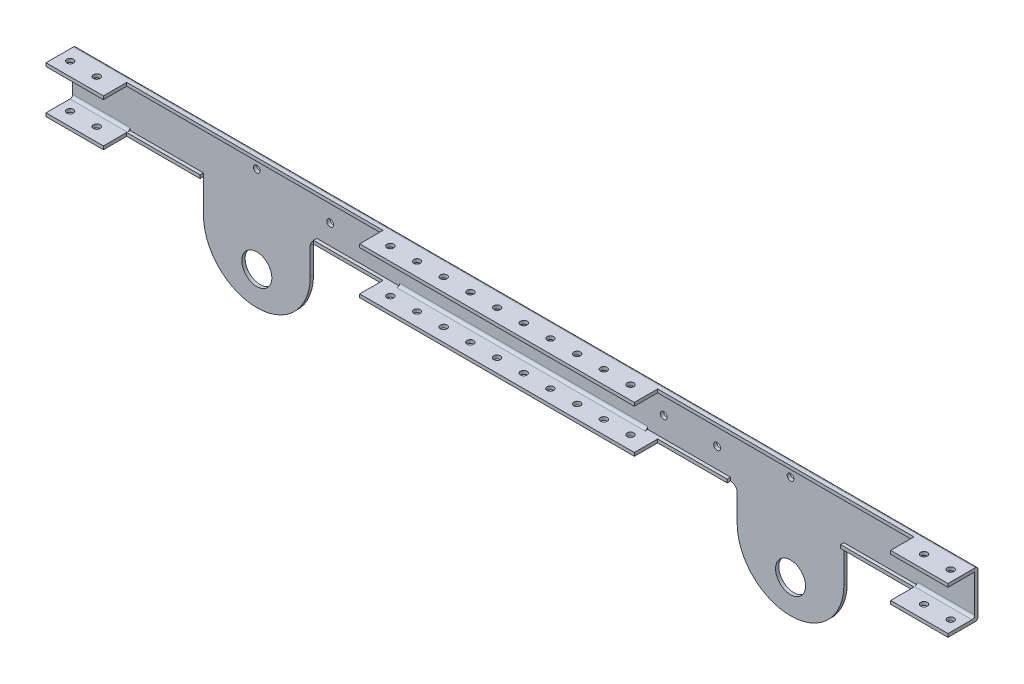
SolidWorks part; units mm, degrees
ref_plane "Front Plane" through (0, 0, 0) normal (0, 0, 1) x (1, 0, 0)
ref_plane "Top Plane" through (0, 0, 0) normal (0, 1, 0) x (1, 0, 0)
ref_plane "Right Plane" through (0, 0, 0) normal (1, 0, 0) x (0, 0, -1)
sketch "Sketch1" plane through (0, 0, 0) normal (0, 0, 1) x (1, 0, 0)
  line L0 (50.8, 0) -> (50.8, 25.4)
  line L1 (-50.8, 0) -> (-50.8, 76.2)
  line L2 (57.15, 31.75) -> (438.15, 31.75)
  line L3 (444.5, 25.4) -> (444.5, 0)
  line L4 (546.1, 0) -> (546.1, 76.2)
  line L5 (-50.8, 76.2) -> (546.1, 76.2)
  arc A0 (-50.8, 0) -> (50.8, 0) centre (0, 0) ccw
  arc A1 (50.8, 25.4) -> (57.15, 31.75) centre (57.15, 25.4) cw
  arc A2 (438.15, 31.75) -> (444.5, 25.4) centre (438.15, 25.4) cw
  arc A3 (444.5, 0) -> (546.1, 0) centre (495.3, 0) ccw
  circle A4 centre (0, 0) radius 6.35
  circle A5 centre (495.3, 0) radius 6.35
  dimension "D1" = 101.6
  dimension "D2" = 6.35
  dimension "D4" = 6.35
  dimension "D6" = 76.2
  dimension "D3" = 381
  dimension "D5" = 25.4
  dimension "D7" = 76.2
extrude "Boss-Extrude1" add sketch "Sketch1" along normal blind 3.175
sketch "Sketch2" plane through (0, 0, 3.175) normal (0, 0, 1) x (1, 0, 0)
  line L0 (-50.8, 76.2) -> (-50.8, 73.025)
  line L1 (-50.8, 76.2) -> (-50.8, 0) construction
  line L2 (546.1, 76.2) -> (-50.8, 76.2)
  line L3 (-50.8, 73.025) -> (546.1, 73.025)
  line L4 (546.1, 0) -> (546.1, 76.2) construction
  line L5 (546.1, 73.025) -> (546.1, 76.2)
  dimension "D1" = 3.175
extrude "Boss-Extrude2" add sketch "Sketch2" along normal blind 25.4
fillet "Fillet1" radius 2.54 2 edges at (247.65, 76.2, 0)
sketch "Sketch3" plane through (0, 76.2, 0) normal (0, 1, 0) x (1, 0, 0)
  line L0 (546.1, -28.575) -> (546.1, -2.54)
  circle A0 centre (527.05, -15.5575) radius 3.2639
  circle A1 centre (501.65, -15.5575) radius 3.2639
  circle A2 centre (476.25, -15.5575) radius 3.2639
  circle A3 centre (450.85, -15.5575) radius 3.2639
  circle A4 centre (425.45, -15.5575) radius 3.2639
  circle A5 centre (400.05, -15.5575) radius 3.2639
  circle A6 centre (374.65, -15.5575) radius 3.2639
  circle A7 centre (349.25, -15.5575) radius 3.2639
  circle A8 centre (323.85, -15.5575) radius 3.2639
  circle A9 centre (298.45, -15.5575) radius 3.2639
  circle A10 centre (273.05, -15.5575) radius 3.2639
  circle A11 centre (247.65, -15.5575) radius 3.2639
  circle A12 centre (222.25, -15.5575) radius 3.2639
  circle A13 centre (196.85, -15.5575) radius 3.2639
  circle A14 centre (171.45, -15.5575) radius 3.2639
  circle A15 centre (146.05, -15.5575) radius 3.2639
  circle A16 centre (120.65, -15.5575) radius 3.2639
  circle A17 centre (95.25, -15.5575) radius 3.2639
  circle A18 centre (69.85, -15.5575) radius 3.2639
  circle A19 centre (44.45, -15.5575) radius 3.2639
  circle A20 centre (19.05, -15.5575) radius 3.2639
  circle A21 centre (-6.35, -15.5575) radius 3.2639
  circle A22 centre (-31.75, -15.5575) radius 3.2639
  dimension "D1" = 19.05
  dimension "D2" = 23
extrude "Cut-Extrude1" cut sketch "Sketch3" against normal blind 25.4 contours A0 | A1 | A2 | A3 | A22 | A21 | A20 | A19 | A18 | A17 | A16 | A15 | A14 | A13 | A12 | A11 | A10 | A9 | A8 | A7 | A6 | A5 | A4 region at (527.05, 76.2, 15.5575) region at (501.65, 76.2, 15.5575) region at (476.25, 76.2, 15.5575) region at (450.85, 76.2, 15.5575) region at (425.45, 76.2, 15.5575) region at (400.05, 76.2, 15.5575) region at (374.65, 76.2, 15.5575) region at (349.25, 76.2, 15.5575) region at (323.85, 76.2, 15.5575) region at (298.45, 76.2, 15.5575) region at (273.05, 76.2, 15.5575) region at (247.65, 76.2, 15.5575) region at (222.25, 76.2, 15.5575) region at (196.85, 76.2, 15.5575) region at (171.45, 76.2, 15.5575) region at (146.05, 76.2, 15.5575) region at (120.65, 76.2, 15.5575) region at (95.25, 76.2, 15.5575) region at (69.85, 76.2, 15.5575) region at (44.45, 76.2, 15.5575) region at (19.05, 76.2, 15.5575) region at (-6.35, 76.2, 15.5575) region at (-31.75, 76.2, 15.5575)
sketch "Sketch5" plane through (0, 0, 0) normal (0, 0, -1) x (-1, 0, 0)
  line L0 (-444.5, 25.4) -> (-444.5, 0) construction
  circle A0 centre (-425.45, 53.975) radius 3.2639
  circle A1 centre (-374.65, 53.975) radius 3.2639
  circle A2 centre (-323.85, 53.975) radius 3.2639
  circle A3 centre (-273.05, 53.975) radius 3.2639
  circle A4 centre (-222.25, 53.975) radius 3.2639
  circle A5 centre (-171.45, 53.975) radius 3.2639
  circle A6 centre (-120.65, 53.975) radius 3.2639
  circle A7 centre (-69.85, 53.975) radius 3.2639
  dimension "D1" = 6.5278
  dimension "D2" = 19.05
  dimension "D3" = 8
extrude "Cut-Extrude2" cut sketch "Sketch5" against normal blind 25.4
sketch "Sketch6" plane through (0, 0, 3.175) normal (0, 0, 1) x (1, 0, 0)
  line L1 (-50.8, 76.2) -> (-82.55, 76.2)
  line L2 (-50.8, 76.2) -> (-50.8, 31.75)
  line L3 (-50.8, 31.75) -> (-82.55, 31.75)
  line L4 (-82.55, 76.2) -> (-82.55, 31.75)
  line L5 (546.1, 76.2) -> (577.85, 76.2)
  line L6 (546.1, 76.2) -> (546.1, 31.75)
  line L7 (546.1, 31.75) -> (577.85, 31.75)
  line L8 (577.85, 76.2) -> (577.85, 31.75)
  dimension "D1" = 31.75
  dimension "D2" = 31.75
extrude "Boss-Extrude3" add sketch "Sketch6" against normal blind 3.175
sketch "Sketch7" plane through (0, 0, 3.175) normal (0, 0, 1) x (1, 0, 0)
  line L1 (57.15, 31.75) -> (438.15, 31.75) construction
  line L2 (-50.8, 73.025) -> (-82.55, 73.025)
  line L3 (-50.8, 73.025) -> (-50.8, 76.2)
  line L4 (-50.8, 76.2) -> (-82.55, 76.2)
  line L5 (-82.55, 31.75) -> (-50.8, 31.75)
  line L6 (-82.55, 31.75) -> (-82.55, 34.925)
  line L7 (-82.55, 34.925) -> (-50.8, 34.925)
  line L8 (-50.8, 31.75) -> (-50.8, 34.925)
  line L9 (577.85, 31.75) -> (577.85, 76.2) construction
  line L10 (546.1, 76.2) -> (577.85, 76.2)
  line L11 (546.1, 76.2) -> (546.1, 73.025)
  line L12 (546.1, 73.025) -> (577.85, 73.025)
  line L13 (577.85, 76.2) -> (577.85, 73.025)
  line L14 (-82.55, 73.025) -> (-82.55, 76.2)
  line L15 (577.85, 31.75) -> (546.1, 31.75)
  line L16 (577.85, 31.75) -> (577.85, 34.925)
  line L17 (577.85, 34.925) -> (546.1, 34.925)
  line L18 (546.1, 31.75) -> (546.1, 34.925)
  line L19 (57.15, 31.75) -> (438.15, 31.75)
  line L20 (57.15, 31.75) -> (57.15, 34.925)
  line L21 (57.15, 34.925) -> (438.15, 34.925)
  line L22 (438.15, 31.75) -> (438.15, 34.925)
  arc A0 (57.15, 31.75) -> (50.8, 25.4) centre (57.15, 25.4) ccw construction
  dimension "D1" = 3.175
  dimension "D2" = 3.175
  dimension "D3" = 3.175
extrude "Boss-Extrude4" add sketch "Sketch7" along normal blind 25.4
fillet "Fillet2" radius 2.54 16 edges at (-50.8, 15.875, 0) (0, -50.8, 0) (50.8, 12.7, 0) (52.6599, 29.8901, 0) (546.1, 15.875, 0) (495.3, -50.8, 0) (444.5, 12.7, 0) (442.6401, 29.8901, 0) (-66.675, 34.925, 3.175) (-66.675, 31.75, 0) (247.65, 31.75, 0) (247.65, 34.925, 3.175) (561.975, 34.925, 3.175) (561.975, 31.75, 0) (561.975, 76.2, 0) (-66.675, 76.2, 0)
sketch "Sketch8" plane through (0, 76.2, 0) normal (0, 1, 0) x (1, 0, 0)
  circle A0 centre (-31.75, -15.5575) radius 3.2639 construction
  circle A1 centre (-31.75, -15.5575) radius 3.2639
  circle A2 centre (-57.15, -15.5575) radius 3.2639
  circle A3 centre (-31.75, -15.5575) radius 3.2639
  circle A4 centre (-6.35, -15.5575) radius 3.2639
  circle A5 centre (19.05, -15.5575) radius 3.2639
  circle A6 centre (44.45, -15.5575) radius 3.2639
  circle A7 centre (69.85, -15.5575) radius 3.2639
  circle A8 centre (95.25, -15.5575) radius 3.2639
  circle A9 centre (120.65, -15.5575) radius 3.2639
  circle A10 centre (146.05, -15.5575) radius 3.2639
  circle A11 centre (171.45, -15.5575) radius 3.2639
  circle A12 centre (196.85, -15.5575) radius 3.2639
  circle A13 centre (222.25, -15.5575) radius 3.2639
  circle A14 centre (247.65, -15.5575) radius 3.2639
  circle A15 centre (273.05, -15.5575) radius 3.2639
  circle A16 centre (298.45, -15.5575) radius 3.2639
  circle A17 centre (323.85, -15.5575) radius 3.2639
  circle A18 centre (349.25, -15.5575) radius 3.2639
  circle A19 centre (374.65, -15.5575) radius 3.2639
  circle A20 centre (400.05, -15.5575) radius 3.2639
  circle A21 centre (425.45, -15.5575) radius 3.2639
  circle A22 centre (450.85, -15.5575) radius 3.2639
  circle A23 centre (476.25, -15.5575) radius 3.2639
  circle A24 centre (501.65, -15.5575) radius 3.2639
  circle A25 centre (527.05, -15.5575) radius 3.2639
  circle A26 centre (-6.35, -15.5575) radius 3.2639
  circle A27 centre (19.05, -15.5575) radius 3.2639
  circle A28 centre (44.45, -15.5575) radius 3.2639
  circle A29 centre (69.85, -15.5575) radius 3.2639
  circle A30 centre (95.25, -15.5575) radius 3.2639
  circle A31 centre (120.65, -15.5575) radius 3.2639
  circle A32 centre (146.05, -15.5575) radius 3.2639
  circle A33 centre (171.45, -15.5575) radius 3.2639
  circle A34 centre (196.85, -15.5575) radius 3.2639
  circle A35 centre (222.25, -15.5575) radius 3.2639
  circle A36 centre (247.65, -15.5575) radius 3.2639
  circle A37 centre (273.05, -15.5575) radius 3.2639
  circle A38 centre (298.45, -15.5575) radius 3.2639
  circle A39 centre (323.85, -15.5575) radius 3.2639
  circle A40 centre (349.25, -15.5575) radius 3.2639
  circle A41 centre (374.65, -15.5575) radius 3.2639
  circle A42 centre (400.05, -15.5575) radius 3.2639
  circle A43 centre (425.45, -15.5575) radius 3.2639
  circle A44 centre (450.85, -15.5575) radius 3.2639
  circle A45 centre (476.25, -15.5575) radius 3.2639
  circle A46 centre (501.65, -15.5575) radius 3.2639
  circle A47 centre (527.05, -15.5575) radius 3.2639
  circle A48 centre (552.45, -15.5575) radius 3.2639
  circle M1 centre (425.45, -15.5575) radius 3.2639
  circle M2 centre (400.05, -15.5575) radius 3.2639
  circle M3 centre (374.65, -15.5575) radius 3.2639
  circle M4 centre (349.25, -15.5575) radius 3.2639
  circle M5 centre (323.85, -15.5575) radius 3.2639
  circle M6 centre (298.45, -15.5575) radius 3.2639
  circle M7 centre (273.05, -15.5575) radius 3.2639
  circle M8 centre (247.65, -15.5575) radius 3.2639
  circle M9 centre (222.25, -15.5575) radius 3.2639
  circle M10 centre (196.85, -15.5575) radius 3.2639
  circle M11 centre (171.45, -15.5575) radius 3.2639
  circle M12 centre (146.05, -15.5575) radius 3.2639
  circle M13 centre (120.65, -15.5575) radius 3.2639
  circle M14 centre (95.25, -15.5575) radius 3.2639
  circle M15 centre (69.85, -15.5575) radius 3.2639
  circle M16 centre (44.45, -15.5575) radius 3.2639
  circle M17 centre (19.05, -15.5575) radius 3.2639
  circle M18 centre (-6.35, -15.5575) radius 3.2639
  circle M19 centre (-31.75, -15.5575) radius 3.2639
  circle M20 centre (450.85, -15.5575) radius 3.2639
  circle M21 centre (476.25, -15.5575) radius 3.2639
  circle M22 centre (501.65, -15.5575) radius 3.2639
  circle M23 centre (527.05, -15.5575) radius 3.2639
  dimension "D1" = 2
  dimension "D2" = 24
extrude "Cut-Extrude3" cut sketch "Sketch8" against normal blind 177.8 contours A2 | M19 | M18 | M17 | M16 | M15 | M14 | M13 | M12 | M11 | M10 | M9 | M8 | M7 | M6 | M5 | M4 | M3 | M2 | M1 | M20 | M21 | A48 | M23 | M22 region at (-31.75, 76.2, 15.5575) region at (-57.15, 76.2, 15.5575) region at (-6.35, 76.2, 15.5575) region at (19.05, 76.2, 15.5575) region at (44.45, 76.2, 15.5575) region at (69.85, 76.2, 15.5575) region at (95.25, 76.2, 15.5575) region at (120.65, 76.2, 15.5575) region at (146.05, 76.2, 15.5575) region at (171.45, 76.2, 15.5575) region at (196.85, 76.2, 15.5575) region at (222.25, 76.2, 15.5575) region at (247.65, 76.2, 15.5575) region at (273.05, 76.2, 15.5575) region at (298.45, 76.2, 15.5575) region at (323.85, 76.2, 15.5575) region at (349.25, 76.2, 15.5575) region at (374.65, 76.2, 15.5575) region at (400.05, 76.2, 15.5575) region at (425.45, 76.2, 15.5575) region at (450.85, 76.2, 15.5575) region at (476.25, 76.2, 15.5575) region at (501.65, 76.2, 15.5575) region at (527.05, 76.2, 15.5575) region at (552.45, 76.2, 15.5575)
sketch "Sketch9" plane through (0, 76.2, 0) normal (0, 1, 0) x (1, 0, 0)
  line L0 (-82.55, -28.575) -> (298.45, -28.575)
  line L1 (577.85, -28.575) -> (-82.55, -28.575) construction
  line L3 (298.45, -28.575) -> (746.3929, -28.575)
  line L4 (298.45, -28.575) -> (298.45, 89.0041)
  line L5 (298.45, 89.0041) -> (746.3929, 89.0041)
  line L6 (746.3929, -28.575) -> (746.3929, 89.0041)
  circle M1 centre (552.45, -15.5575) radius 3.2639
  circle M3 centre (425.45, -15.5575) radius 3.2639
  circle M4 centre (400.05, -15.5575) radius 3.2639
  circle M5 centre (374.65, -15.5575) radius 3.2639
  circle M6 centre (349.25, -15.5575) radius 3.2639
  circle M7 centre (323.85, -15.5575) radius 3.2639
  circle M8 centre (298.45, -15.5575) radius 3.2639
  circle M22 centre (450.85, -15.5575) radius 3.2639
  circle M23 centre (476.25, -15.5575) radius 3.2639
  circle M24 centre (501.65, -15.5575) radius 3.2639
  circle M25 centre (527.05, -15.5575) radius 3.2639
  line M26 (577.85, -28.575) -> (577.85, -2.54)
  line M27 (577.85, -2.54) -> (546.1, -2.54)
  line M28 (546.1, -2.54) -> (-50.8, -2.54)
  line M31 (-82.55, -28.575) -> (577.85, -28.575)
extrude "Cut-Extrude5" cut sketch "Sketch9" against normal blind 432.308 contours L4 M31 M26 M27 M28 M8 M4 M6 M22 M24 M25 M23 M7 M5 M3 M1 | L3 L6 L5 L4 M28 M27 M26 region at (438.4843, 76.2, 15.5575) region at (535.9254, 76.2, -37.5492)
mirror "Mirror4" about plane through (298.45, -356.108, 0) normal (1, 0, 0) of bodies 110
sketch "Sketch10" plane through (-82.55, 0, 0) normal (-1, 0, 0) x (0, 0, 1)
  line L8 (0, 73.66) -> (0, 34.29)
  line L9 (2.54, 31.75) -> (28.575, 31.75)
  line L10 (28.575, 31.75) -> (28.575, 34.925)
  line L11 (28.575, 34.925) -> (5.715, 34.925)
  line L12 (3.175, 37.465) -> (3.175, 73.025)
  line L13 (3.175, 73.025) -> (28.575, 73.025)
  line L14 (28.575, 73.025) -> (28.575, 76.2)
  line L15 (28.575, 76.2) -> (2.54, 76.2)
  line L16 (0, 73.66) -> (0, 34.29)
  line L17 (2.54, 31.75) -> (28.575, 31.75)
  line L18 (28.575, 31.75) -> (28.575, 34.925)
  line L19 (28.575, 34.925) -> (5.715, 34.925)
  line L20 (3.175, 37.465) -> (3.175, 73.025)
  line L21 (3.175, 73.025) -> (28.575, 73.025)
  line L22 (28.575, 73.025) -> (28.575, 76.2)
  line L23 (28.575, 76.2) -> (2.54, 76.2)
  arc A3 (0, 34.29) -> (2.54, 31.75) centre (2.54, 34.29) ccw
  arc A4 (3.175, 37.465) -> (5.715, 34.925) centre (5.715, 37.465) ccw
  arc A5 (2.54, 76.2) -> (0, 73.66) centre (2.54, 73.66) ccw
  arc A6 (0, 34.29) -> (2.54, 31.75) centre (2.54, 34.29) ccw
  arc A7 (3.175, 37.465) -> (5.715, 34.925) centre (5.715, 37.465) ccw
  arc A8 (2.54, 76.2) -> (0, 73.66) centre (2.54, 73.66) ccw
  dimension "D1" = 0
extrude "Boss-Extrude6" add sketch "Sketch10" along normal blind 66.675
sketch "Sketch11" plane through (679.45, 0, 0) normal (1, 0, 0) x (0, 0, -1)
  line L8 (0, 34.29) -> (0, 73.66)
  line L9 (-2.54, 76.2) -> (-28.575, 76.2)
  line L10 (-28.575, 76.2) -> (-28.575, 73.025)
  line L11 (-28.575, 73.025) -> (-3.175, 73.025)
  line L12 (-3.175, 73.025) -> (-3.175, 37.465)
  line L13 (-5.715, 34.925) -> (-28.575, 34.925)
  line L14 (-28.575, 34.925) -> (-28.575, 31.75)
  line L15 (-28.575, 31.75) -> (-2.54, 31.75)
  line L16 (0, 34.29) -> (0, 73.66)
  line L17 (-2.54, 76.2) -> (-28.575, 76.2)
  line L18 (-28.575, 76.2) -> (-28.575, 73.025)
  line L19 (-28.575, 73.025) -> (-3.175, 73.025)
  line L20 (-3.175, 73.025) -> (-3.175, 37.465)
  line L21 (-5.715, 34.925) -> (-28.575, 34.925)
  line L22 (-28.575, 34.925) -> (-28.575, 31.75)
  line L23 (-28.575, 31.75) -> (-2.54, 31.75)
  arc A3 (0, 73.66) -> (-2.54, 76.2) centre (-2.54, 73.66) ccw
  arc A4 (-5.715, 34.925) -> (-3.175, 37.465) centre (-5.715, 37.465) ccw
  arc A5 (-2.54, 31.75) -> (0, 34.29) centre (-2.54, 34.29) ccw
  arc A6 (0, 73.66) -> (-2.54, 76.2) centre (-2.54, 73.66) ccw
  arc A7 (-5.715, 34.925) -> (-3.175, 37.465) centre (-5.715, 37.465) ccw
  arc A8 (-2.54, 31.75) -> (0, 34.29) centre (-2.54, 34.29) ccw
  dimension "D1" = 0
extrude "Boss-Extrude7" add sketch "Sketch11" along normal blind 66.675
sketch "Sketch12" plane through (0, 0, 3.175) normal (0, 0, 1) x (1, 0, 0)
  line L1 (114.3, 114.3) -> (-114.3, 114.3)
  line L2 (460.9211, 135.1062) -> (717.55, 135.1062)
  line L3 (460.9211, 135.1062) -> (460.9211, -117.6098)
  line L4 (482.6, 135.1062) -> (692.7253, 135.1062)
  line L5 (692.7253, 135.1062) -> (711.2, 135.1062)
  line L6 (460.9211, -117.6098) -> (717.55, -117.6098)
  line L7 (717.55, 135.1062) -> (717.55, -117.6098)
  line L8 (482.6, 135.1062) -> (460.9211, 135.1062)
  line L11 (460.9211, 135.1062) -> (460.9211, -59.2459)
  line L12 (711.2, 135.1062) -> (717.55, 135.1062)
  line L15 (717.55, 135.1062) -> (717.55, 3.7539)
  line L16 (114.3, 114.3) -> (135.9789, 114.3)
  line L17 (114.3, 0) -> (114.3, -15.4588)
  line L18 (114.3, -15.4588) -> (135.9789, -15.4588)
  line L19 (135.9789, 114.3) -> (135.9789, -15.4588)
  line L20 (-114.3, 114.3) -> (-120.65, 114.3)
  line L21 (-114.3, 0) -> (-114.3, -7.9863)
  line L22 (-114.3, -7.9863) -> (-120.65, -7.9863)
  line L23 (-120.65, 114.3) -> (-120.65, -7.9863)
  arc A0 (-114.3, 0) -> (114.3, 0) centre (0, 0) ccw
  circle M1 centre (0, 0) radius 6.35
  circle M5 centre (120.65, 53.975) radius 3.2639
  circle M6 centre (69.85, 53.975) radius 3.2639
  line M7 (57.15, 37.465) -> (539.75, 37.465)
  line M8 (539.75, 37.465) -> (539.75, 31.75)
  arc M9 (539.75, 31.75) -> (546.1, 25.4) centre (539.75, 25.4) cw
  line M10 (546.1, 25.4) -> (546.1, 0)
  arc M11 (546.1, 0) -> (647.7, 0) centre (596.9, 0) ccw
  line M12 (647.7, 0) -> (647.7, 31.75)
  line M13 (647.7, 31.75) -> (647.7, 37.465)
  line M14 (647.7, 37.465) -> (746.125, 37.465)
  line M16 (746.125, 73.025) -> (647.7, 73.025)
  line M17 (647.7, 73.025) -> (647.7, 70.485)
  line M18 (647.7, 70.485) -> (-50.8, 70.485)
  line M19 (-50.8, 70.485) -> (-50.8, 73.025)
  line M20 (-50.8, 73.025) -> (-149.225, 73.025)
  line M22 (-149.225, 37.465) -> (-50.8, 37.465)
  line M23 (-50.8, 37.465) -> (-50.8, 31.75)
  line M24 (-50.8, 31.75) -> (-50.8, 0)
  arc M25 (-50.8, 0) -> (50.8, 0) centre (0, 0) ccw
  line M26 (50.8, 0) -> (50.8, 25.4)
  arc M27 (50.8, 25.4) -> (57.15, 31.75) centre (57.15, 25.4) cw
  line M28 (57.15, 31.75) -> (57.15, 37.465)
  circle M29 centre (596.9, 0) radius 6.35
  circle M33 centre (476.25, 53.975) radius 3.2639
  circle M34 centre (527.05, 53.975) radius 3.2639
  dimension "D1" = 13.335
  dimension "D2" = 6.35
  dimension "D3" = 13.335
  dimension "D4" = 6.35
extrude "Cut-Extrude8" cut sketch "Sketch12" along normal blind 66.675 contours L7 L3 L6 M14 M13 M12 M11 M10 M9 M8 M7 | L7 L3 M16 M17 M18 M7 M8 M9 M10 M11 M12 M13 M14 M34 M33 M29 | L7 L2 L3 M18 M17 M16 | L21 A0 L17 L18 L19 L23 L22 M7 M28 M27 M26 M25 M24 M23 M22 | L23 L19 M20 M22 M23 M24 M25 M26 M27 M28 M7 M18 M19 M6 M5 M1 | L20 L23 L19 L16 L1 M20 M19 M18 region at (9.1616, 92.7234, 3.175) region at (2.7974, 27.6189, 3.175) region at (132.9974, 11.0031, 3.175) region at (594.1026, 27.6189, 3.175) region at (588.2256, 103.1313, 3.175) region at (500.3355, 34.4666, 3.175)
sketch "Sketch13" plane through (0, 76.2, 0) normal (0, 1, 0) x (1, 0, 0)
  circle A0 centre (146.05, -15.5575) radius 3.2639 construction
  circle A1 centre (146.05, -15.5575) radius 3.2639
sketch "Sketch14" plane through (746.125, 0, 0) normal (1, 0, 0) x (0, 0, -1)
  line L8 (0, 34.29) -> (0, 73.66)
  line L9 (-2.54, 76.2) -> (-28.575, 76.2)
  line L10 (-28.575, 76.2) -> (-28.575, 73.025)
  line L11 (-28.575, 73.025) -> (-3.175, 73.025)
  line L12 (-3.175, 73.025) -> (-3.175, 37.465)
  line L13 (-5.715, 34.925) -> (-28.575, 34.925)
  line L14 (-28.575, 34.925) -> (-28.575, 31.75)
  line L15 (-28.575, 31.75) -> (-2.54, 31.75)
  line L16 (0, 34.29) -> (0, 73.66)
  line L17 (-2.54, 76.2) -> (-28.575, 76.2)
  line L18 (-28.575, 76.2) -> (-28.575, 73.025)
  line L19 (-28.575, 73.025) -> (-3.175, 73.025)
  line L20 (-3.175, 73.025) -> (-3.175, 37.465)
  line L21 (-5.715, 34.925) -> (-28.575, 34.925)
  line L22 (-28.575, 34.925) -> (-28.575, 31.75)
  line L23 (-28.575, 31.75) -> (-2.54, 31.75)
  arc A3 (-2.54, 31.75) -> (0, 34.29) centre (-2.54, 34.29) ccw
  arc A4 (0, 73.66) -> (-2.54, 76.2) centre (-2.54, 73.66) ccw
  arc A5 (-5.715, 34.925) -> (-3.175, 37.465) centre (-5.715, 37.465) ccw
  arc A6 (-2.54, 31.75) -> (0, 34.29) centre (-2.54, 34.29) ccw
  arc A7 (0, 73.66) -> (-2.54, 76.2) centre (-2.54, 73.66) ccw
  arc A8 (-5.715, 34.925) -> (-3.175, 37.465) centre (-5.715, 37.465) ccw
  dimension "D1" = 0
extrude "Boss-Extrude8" add sketch "Sketch14" along normal blind 19.05
sketch "Sketch15" plane through (-149.225, 0, 0) normal (-1, 0, 0) x (0, 0, 1)
  line L8 (0, 73.66) -> (0, 34.29)
  line L9 (2.54, 31.75) -> (28.575, 31.75)
  line L10 (28.575, 31.75) -> (28.575, 34.925)
  line L11 (28.575, 34.925) -> (5.715, 34.925)
  line L12 (3.175, 37.465) -> (3.175, 73.025)
  line L13 (3.175, 73.025) -> (28.575, 73.025)
  line L14 (28.575, 73.025) -> (28.575, 76.2)
  line L15 (28.575, 76.2) -> (2.54, 76.2)
  line L16 (0, 73.66) -> (0, 34.29)
  line L17 (2.54, 31.75) -> (28.575, 31.75)
  line L18 (28.575, 31.75) -> (28.575, 34.925)
  line L19 (28.575, 34.925) -> (5.715, 34.925)
  line L20 (3.175, 37.465) -> (3.175, 73.025)
  line L21 (3.175, 73.025) -> (28.575, 73.025)
  line L22 (28.575, 73.025) -> (28.575, 76.2)
  line L23 (28.575, 76.2) -> (2.54, 76.2)
  arc A3 (2.54, 76.2) -> (0, 73.66) centre (2.54, 73.66) ccw
  arc A4 (0, 34.29) -> (2.54, 31.75) centre (2.54, 34.29) ccw
  arc A5 (3.175, 37.465) -> (5.715, 34.925) centre (5.715, 37.465) ccw
  arc A6 (2.54, 76.2) -> (0, 73.66) centre (2.54, 73.66) ccw
  arc A7 (0, 34.29) -> (2.54, 31.75) centre (2.54, 34.29) ccw
  arc A8 (3.175, 37.465) -> (5.715, 34.925) centre (5.715, 37.465) ccw
  dimension "D1" = 0
extrude "Boss-Extrude9" add sketch "Sketch15" along normal blind 19.05
sketch "Sketch16" plane through (0, 76.2, 0) normal (0, 1, 0) x (1, 0, 0)
  circle A0 centre (146.05, -15.5575) radius 3.2639 construction
  circle A1 centre (146.05, -15.5575) radius 3.2639
  circle A2 centre (171.45, -15.5575) radius 3.2639
  circle A3 centre (196.85, -15.5575) radius 3.2639
  circle A4 centre (222.25, -15.5575) radius 3.2639
  circle A5 centre (247.65, -15.5575) radius 3.2639
  circle A6 centre (273.05, -15.5575) radius 3.2639
  circle A7 centre (298.45, -15.5575) radius 3.2639
  circle A8 centre (323.85, -15.5575) radius 3.2639
  circle A9 centre (349.25, -15.5575) radius 3.2639
  circle A10 centre (374.65, -15.5575) radius 3.2639
  circle A11 centre (400.05, -15.5575) radius 3.2639
  circle A12 centre (425.45, -15.5575) radius 3.2639
  circle A13 centre (450.85, -15.5575) radius 3.2639
  circle A14 centre (476.25, -15.5575) radius 3.2639
  circle A15 centre (501.65, -15.5575) radius 3.2639
  circle A16 centre (527.05, -15.5575) radius 3.2639
  circle A17 centre (552.45, -15.5575) radius 3.2639
  circle A18 centre (577.85, -15.5575) radius 3.2639
  circle A19 centre (603.25, -15.5575) radius 3.2639
  circle A20 centre (628.65, -15.5575) radius 3.2639
  circle A21 centre (654.05, -15.5575) radius 3.2639
  circle A22 centre (679.45, -15.5575) radius 3.2639
  circle A23 centre (704.85, -15.5575) radius 3.2639
  circle A24 centre (730.25, -15.5575) radius 3.2639
  circle A25 centre (755.65, -15.5575) radius 3.2639
  circle A26 centre (146.05, -15.5575) radius 3.2639
  circle A27 centre (171.45, -15.5575) radius 3.2639
  circle A28 centre (196.85, -15.5575) radius 3.2639
  circle A29 centre (222.25, -15.5575) radius 3.2639
  circle A30 centre (247.65, -15.5575) radius 3.2639
  circle A31 centre (273.05, -15.5575) radius 3.2639
  circle A32 centre (298.45, -15.5575) radius 3.2639
  circle A33 centre (323.85, -15.5575) radius 3.2639
  circle A34 centre (349.25, -15.5575) radius 3.2639
  circle A35 centre (374.65, -15.5575) radius 3.2639
  circle A36 centre (400.05, -15.5575) radius 3.2639
  circle A37 centre (425.45, -15.5575) radius 3.2639
  circle A38 centre (450.85, -15.5575) radius 3.2639
  circle A39 centre (476.25, -15.5575) radius 3.2639
  circle A40 centre (501.65, -15.5575) radius 3.2639
  circle A41 centre (527.05, -15.5575) radius 3.2639
  circle A42 centre (552.45, -15.5575) radius 3.2639
  circle A43 centre (577.85, -15.5575) radius 3.2639
  circle A44 centre (603.25, -15.5575) radius 3.2639
  circle A45 centre (628.65, -15.5575) radius 3.2639
  circle A46 centre (654.05, -15.5575) radius 3.2639
  circle A47 centre (679.45, -15.5575) radius 3.2639
  circle A48 centre (704.85, -15.5575) radius 3.2639
  circle A49 centre (730.25, -15.5575) radius 3.2639
  circle A50 centre (120.65, -15.5575) radius 3.2639
  circle A51 centre (146.05, -15.5575) radius 3.2639
  circle A52 centre (171.45, -15.5575) radius 3.2639
  circle A53 centre (196.85, -15.5575) radius 3.2639
  circle A54 centre (222.25, -15.5575) radius 3.2639
  circle A55 centre (247.65, -15.5575) radius 3.2639
  circle A56 centre (273.05, -15.5575) radius 3.2639
  circle A57 centre (298.45, -15.5575) radius 3.2639
  circle A58 centre (323.85, -15.5575) radius 3.2639
  circle A59 centre (349.25, -15.5575) radius 3.2639
  circle A60 centre (374.65, -15.5575) radius 3.2639
  circle A61 centre (400.05, -15.5575) radius 3.2639
  circle A62 centre (425.45, -15.5575) radius 3.2639
  circle A63 centre (450.85, -15.5575) radius 3.2639
  circle A64 centre (476.25, -15.5575) radius 3.2639
  circle A65 centre (501.65, -15.5575) radius 3.2639
  circle A66 centre (527.05, -15.5575) radius 3.2639
  circle A67 centre (552.45, -15.5575) radius 3.2639
  circle A68 centre (577.85, -15.5575) radius 3.2639
  circle A69 centre (603.25, -15.5575) radius 3.2639
  circle A70 centre (628.65, -15.5575) radius 3.2639
  circle A71 centre (654.05, -15.5575) radius 3.2639
  circle A72 centre (679.45, -15.5575) radius 3.2639
  circle A73 centre (704.85, -15.5575) radius 3.2639
  circle A74 centre (95.25, -15.5575) radius 3.2639
  circle A75 centre (120.65, -15.5575) radius 3.2639
  circle A76 centre (146.05, -15.5575) radius 3.2639
  circle A77 centre (171.45, -15.5575) radius 3.2639
  circle A78 centre (196.85, -15.5575) radius 3.2639
  circle A79 centre (222.25, -15.5575) radius 3.2639
  circle A80 centre (247.65, -15.5575) radius 3.2639
  circle A81 centre (273.05, -15.5575) radius 3.2639
  circle A82 centre (298.45, -15.5575) radius 3.2639
  circle A83 centre (323.85, -15.5575) radius 3.2639
  circle A84 centre (349.25, -15.5575) radius 3.2639
  circle A85 centre (374.65, -15.5575) radius 3.2639
  circle A86 centre (400.05, -15.5575) radius 3.2639
  circle A87 centre (425.45, -15.5575) radius 3.2639
  circle A88 centre (450.85, -15.5575) radius 3.2639
  circle A89 centre (476.25, -15.5575) radius 3.2639
  circle A90 centre (501.65, -15.5575) radius 3.2639
  circle A91 centre (527.05, -15.5575) radius 3.2639
  circle A92 centre (552.45, -15.5575) radius 3.2639
  circle A93 centre (577.85, -15.5575) radius 3.2639
  circle A94 centre (603.25, -15.5575) radius 3.2639
  circle A95 centre (628.65, -15.5575) radius 3.2639
  circle A96 centre (654.05, -15.5575) radius 3.2639
  circle A97 centre (679.45, -15.5575) radius 3.2639
  circle A98 centre (69.85, -15.5575) radius 3.2639
  circle A99 centre (95.25, -15.5575) radius 3.2639
  circle A100 centre (120.65, -15.5575) radius 3.2639
  circle A101 centre (146.05, -15.5575) radius 3.2639
  circle A102 centre (171.45, -15.5575) radius 3.2639
  circle A103 centre (196.85, -15.5575) radius 3.2639
  circle A104 centre (222.25, -15.5575) radius 3.2639
  circle A105 centre (247.65, -15.5575) radius 3.2639
  circle A106 centre (273.05, -15.5575) radius 3.2639
  circle A107 centre (298.45, -15.5575) radius 3.2639
  circle A108 centre (323.85, -15.5575) radius 3.2639
  circle A109 centre (349.25, -15.5575) radius 3.2639
  circle A110 centre (374.65, -15.5575) radius 3.2639
  circle A111 centre (400.05, -15.5575) radius 3.2639
  circle A112 centre (425.45, -15.5575) radius 3.2639
  circle A113 centre (450.85, -15.5575) radius 3.2639
  circle A114 centre (476.25, -15.5575) radius 3.2639
  circle A115 centre (501.65, -15.5575) radius 3.2639
  circle A116 centre (527.05, -15.5575) radius 3.2639
  circle A117 centre (552.45, -15.5575) radius 3.2639
  circle A118 centre (577.85, -15.5575) radius 3.2639
  circle A119 centre (603.25, -15.5575) radius 3.2639
  circle A120 centre (628.65, -15.5575) radius 3.2639
  circle A121 centre (654.05, -15.5575) radius 3.2639
  circle A122 centre (44.45, -15.5575) radius 3.2639
  circle A123 centre (69.85, -15.5575) radius 3.2639
  circle A124 centre (95.25, -15.5575) radius 3.2639
  circle A125 centre (120.65, -15.5575) radius 3.2639
  circle A126 centre (146.05, -15.5575) radius 3.2639
  circle A127 centre (171.45, -15.5575) radius 3.2639
  circle A128 centre (196.85, -15.5575) radius 3.2639
  circle A129 centre (222.25, -15.5575) radius 3.2639
  circle A130 centre (247.65, -15.5575) radius 3.2639
  circle A131 centre (273.05, -15.5575) radius 3.2639
  circle A132 centre (298.45, -15.5575) radius 3.2639
  circle A133 centre (323.85, -15.5575) radius 3.2639
  circle A134 centre (349.25, -15.5575) radius 3.2639
  circle A135 centre (374.65, -15.5575) radius 3.2639
  circle A136 centre (400.05, -15.5575) radius 3.2639
  circle A137 centre (425.45, -15.5575) radius 3.2639
  circle A138 centre (450.85, -15.5575) radius 3.2639
  circle A139 centre (476.25, -15.5575) radius 3.2639
  circle A140 centre (501.65, -15.5575) radius 3.2639
  circle A141 centre (527.05, -15.5575) radius 3.2639
  circle A142 centre (552.45, -15.5575) radius 3.2639
  circle A143 centre (577.85, -15.5575) radius 3.2639
  circle A144 centre (603.25, -15.5575) radius 3.2639
  circle A145 centre (628.65, -15.5575) radius 3.2639
  circle A146 centre (19.05, -15.5575) radius 3.2639
  circle A147 centre (44.45, -15.5575) radius 3.2639
  circle A148 centre (69.85, -15.5575) radius 3.2639
  circle A149 centre (95.25, -15.5575) radius 3.2639
  circle A150 centre (120.65, -15.5575) radius 3.2639
  circle A151 centre (146.05, -15.5575) radius 3.2639
  circle A152 centre (171.45, -15.5575) radius 3.2639
  circle A153 centre (196.85, -15.5575) radius 3.2639
  circle A154 centre (222.25, -15.5575) radius 3.2639
  circle A155 centre (247.65, -15.5575) radius 3.2639
  circle A156 centre (273.05, -15.5575) radius 3.2639
  circle A157 centre (298.45, -15.5575) radius 3.2639
  circle A158 centre (323.85, -15.5575) radius 3.2639
  circle A159 centre (349.25, -15.5575) radius 3.2639
  circle A160 centre (374.65, -15.5575) radius 3.2639
  circle A161 centre (400.05, -15.5575) radius 3.2639
  circle A162 centre (425.45, -15.5575) radius 3.2639
  circle A163 centre (450.85, -15.5575) radius 3.2639
  circle A164 centre (476.25, -15.5575) radius 3.2639
  circle A165 centre (501.65, -15.5575) radius 3.2639
  circle A166 centre (527.05, -15.5575) radius 3.2639
  circle A167 centre (552.45, -15.5575) radius 3.2639
  circle A168 centre (577.85, -15.5575) radius 3.2639
  circle A169 centre (603.25, -15.5575) radius 3.2639
  circle A170 centre (-6.35, -15.5575) radius 3.2639
  circle A171 centre (19.05, -15.5575) radius 3.2639
  circle A172 centre (44.45, -15.5575) radius 3.2639
  circle A173 centre (69.85, -15.5575) radius 3.2639
  circle A174 centre (95.25, -15.5575) radius 3.2639
  circle A175 centre (120.65, -15.5575) radius 3.2639
  circle A176 centre (146.05, -15.5575) radius 3.2639
  circle A177 centre (171.45, -15.5575) radius 3.2639
  circle A178 centre (196.85, -15.5575) radius 3.2639
  circle A179 centre (222.25, -15.5575) radius 3.2639
  circle A180 centre (247.65, -15.5575) radius 3.2639
  circle A181 centre (273.05, -15.5575) radius 3.2639
  circle A182 centre (298.45, -15.5575) radius 3.2639
  circle A183 centre (323.85, -15.5575) radius 3.2639
  circle A184 centre (349.25, -15.5575) radius 3.2639
  circle A185 centre (374.65, -15.5575) radius 3.2639
  circle A186 centre (400.05, -15.5575) radius 3.2639
  circle A187 centre (425.45, -15.5575) radius 3.2639
  circle A188 centre (450.85, -15.5575) radius 3.2639
  circle A189 centre (476.25, -15.5575) radius 3.2639
  circle A190 centre (501.65, -15.5575) radius 3.2639
  circle A191 centre (527.05, -15.5575) radius 3.2639
  circle A192 centre (552.45, -15.5575) radius 3.2639
  circle A193 centre (577.85, -15.5575) radius 3.2639
  circle A194 centre (-31.75, -15.5575) radius 3.2639
  circle A195 centre (-6.35, -15.5575) radius 3.2639
  circle A196 centre (19.05, -15.5575) radius 3.2639
  circle A197 centre (44.45, -15.5575) radius 3.2639
  circle A198 centre (69.85, -15.5575) radius 3.2639
  circle A199 centre (95.25, -15.5575) radius 3.2639
  circle A200 centre (120.65, -15.5575) radius 3.2639
  circle A201 centre (146.05, -15.5575) radius 3.2639
  circle A202 centre (171.45, -15.5575) radius 3.2639
  circle A203 centre (196.85, -15.5575) radius 3.2639
  circle A204 centre (222.25, -15.5575) radius 3.2639
  circle A205 centre (247.65, -15.5575) radius 3.2639
  circle A206 centre (273.05, -15.5575) radius 3.2639
  circle A207 centre (298.45, -15.5575) radius 3.2639
  circle A208 centre (323.85, -15.5575) radius 3.2639
  circle A209 centre (349.25, -15.5575) radius 3.2639
  circle A210 centre (374.65, -15.5575) radius 3.2639
  circle A211 centre (400.05, -15.5575) radius 3.2639
  circle A212 centre (425.45, -15.5575) radius 3.2639
  circle A213 centre (450.85, -15.5575) radius 3.2639
  circle A214 centre (476.25, -15.5575) radius 3.2639
  circle A215 centre (501.65, -15.5575) radius 3.2639
  circle A216 centre (527.05, -15.5575) radius 3.2639
  circle A217 centre (552.45, -15.5575) radius 3.2639
  circle A218 centre (-57.15, -15.5575) radius 3.2639
  circle A219 centre (-31.75, -15.5575) radius 3.2639
  circle A220 centre (-6.35, -15.5575) radius 3.2639
  circle A221 centre (19.05, -15.5575) radius 3.2639
  circle A222 centre (44.45, -15.5575) radius 3.2639
  circle A223 centre (69.85, -15.5575) radius 3.2639
  circle A224 centre (95.25, -15.5575) radius 3.2639
  circle A225 centre (120.65, -15.5575) radius 3.2639
  circle A226 centre (146.05, -15.5575) radius 3.2639
  circle A227 centre (171.45, -15.5575) radius 3.2639
  circle A228 centre (196.85, -15.5575) radius 3.2639
  circle A229 centre (222.25, -15.5575) radius 3.2639
  circle A230 centre (247.65, -15.5575) radius 3.2639
  circle A231 centre (273.05, -15.5575) radius 3.2639
  circle A232 centre (298.45, -15.5575) radius 3.2639
  circle A233 centre (323.85, -15.5575) radius 3.2639
  circle A234 centre (349.25, -15.5575) radius 3.2639
  circle A235 centre (374.65, -15.5575) radius 3.2639
  circle A236 centre (400.05, -15.5575) radius 3.2639
  circle A237 centre (425.45, -15.5575) radius 3.2639
  circle A238 centre (450.85, -15.5575) radius 3.2639
  circle A239 centre (476.25, -15.5575) radius 3.2639
  circle A240 centre (501.65, -15.5575) radius 3.2639
  circle A241 centre (527.05, -15.5575) radius 3.2639
  circle A242 centre (-82.55, -15.5575) radius 3.2639
  circle A243 centre (-57.15, -15.5575) radius 3.2639
  circle A244 centre (-31.75, -15.5575) radius 3.2639
  circle A245 centre (-6.35, -15.5575) radius 3.2639
  circle A246 centre (19.05, -15.5575) radius 3.2639
  circle A247 centre (44.45, -15.5575) radius 3.2639
  circle A248 centre (69.85, -15.5575) radius 3.2639
  circle A249 centre (95.25, -15.5575) radius 3.2639
  circle A250 centre (120.65, -15.5575) radius 3.2639
  circle A251 centre (146.05, -15.5575) radius 3.2639
  circle A252 centre (171.45, -15.5575) radius 3.2639
  circle A253 centre (196.85, -15.5575) radius 3.2639
  circle A254 centre (222.25, -15.5575) radius 3.2639
  circle A255 centre (247.65, -15.5575) radius 3.2639
  circle A256 centre (273.05, -15.5575) radius 3.2639
  circle A257 centre (298.45, -15.5575) radius 3.2639
  circle A258 centre (323.85, -15.5575) radius 3.2639
  circle A259 centre (349.25, -15.5575) radius 3.2639
  circle A260 centre (374.65, -15.5575) radius 3.2639
  circle A261 centre (400.05, -15.5575) radius 3.2639
  circle A262 centre (425.45, -15.5575) radius 3.2639
  circle A263 centre (450.85, -15.5575) radius 3.2639
  circle A264 centre (476.25, -15.5575) radius 3.2639
  circle A265 centre (501.65, -15.5575) radius 3.2639
  circle A266 centre (-107.95, -15.5575) radius 3.2639
  circle A267 centre (-82.55, -15.5575) radius 3.2639
  circle A268 centre (-57.15, -15.5575) radius 3.2639
  circle A269 centre (-31.75, -15.5575) radius 3.2639
  circle A270 centre (-6.35, -15.5575) radius 3.2639
  circle A271 centre (19.05, -15.5575) radius 3.2639
  circle A272 centre (44.45, -15.5575) radius 3.2639
  circle A273 centre (69.85, -15.5575) radius 3.2639
  circle A274 centre (95.25, -15.5575) radius 3.2639
  circle A275 centre (120.65, -15.5575) radius 3.2639
  circle A276 centre (146.05, -15.5575) radius 3.2639
  circle A277 centre (171.45, -15.5575) radius 3.2639
  circle A278 centre (196.85, -15.5575) radius 3.2639
  circle A279 centre (222.25, -15.5575) radius 3.2639
  circle A280 centre (247.65, -15.5575) radius 3.2639
  circle A281 centre (273.05, -15.5575) radius 3.2639
  circle A282 centre (298.45, -15.5575) radius 3.2639
  circle A283 centre (323.85, -15.5575) radius 3.2639
  circle A284 centre (349.25, -15.5575) radius 3.2639
  circle A285 centre (374.65, -15.5575) radius 3.2639
  circle A286 centre (400.05, -15.5575) radius 3.2639
  circle A287 centre (425.45, -15.5575) radius 3.2639
  circle A288 centre (450.85, -15.5575) radius 3.2639
  circle A289 centre (476.25, -15.5575) radius 3.2639
  circle A290 centre (-133.35, -15.5575) radius 3.2639
  circle A291 centre (-107.95, -15.5575) radius 3.2639
  circle A292 centre (-82.55, -15.5575) radius 3.2639
  circle A293 centre (-57.15, -15.5575) radius 3.2639
  circle A294 centre (-31.75, -15.5575) radius 3.2639
  circle A295 centre (-6.35, -15.5575) radius 3.2639
  circle A296 centre (19.05, -15.5575) radius 3.2639
  circle A297 centre (44.45, -15.5575) radius 3.2639
  circle A298 centre (69.85, -15.5575) radius 3.2639
  circle A299 centre (95.25, -15.5575) radius 3.2639
  circle A300 centre (120.65, -15.5575) radius 3.2639
  circle A301 centre (146.05, -15.5575) radius 3.2639
  circle A302 centre (171.45, -15.5575) radius 3.2639
  circle A303 centre (196.85, -15.5575) radius 3.2639
  circle A304 centre (222.25, -15.5575) radius 3.2639
  circle A305 centre (247.65, -15.5575) radius 3.2639
  circle A306 centre (273.05, -15.5575) radius 3.2639
  circle A307 centre (298.45, -15.5575) radius 3.2639
  circle A308 centre (323.85, -15.5575) radius 3.2639
  circle A309 centre (349.25, -15.5575) radius 3.2639
  circle A310 centre (374.65, -15.5575) radius 3.2639
  circle A311 centre (400.05, -15.5575) radius 3.2639
  circle A312 centre (425.45, -15.5575) radius 3.2639
  circle A313 centre (450.85, -15.5575) radius 3.2639
  circle A314 centre (120.65, -15.5575) radius 3.2639
  circle A315 centre (95.25, -15.5575) radius 3.2639
  circle A316 centre (69.85, -15.5575) radius 3.2639
  circle A317 centre (44.45, -15.5575) radius 3.2639
  circle A318 centre (19.05, -15.5575) radius 3.2639
  circle A319 centre (-6.35, -15.5575) radius 3.2639
  circle A320 centre (-31.75, -15.5575) radius 3.2639
  circle A321 centre (-57.15, -15.5575) radius 3.2639
  circle A322 centre (-82.55, -15.5575) radius 3.2639
  circle A323 centre (-107.95, -15.5575) radius 3.2639
  circle A324 centre (-133.35, -15.5575) radius 3.2639
  circle A325 centre (-158.75, -15.5575) radius 3.2639
  dimension "D1" = 25
  dimension "D2" = 13
extrude "Cut-Extrude9" cut sketch "Sketch16" against normal blind 133.096
sketch "Sketch17" plane through (0, 0, 0) normal (0, 0, -1) x (-1, 0, 0)
  line L0 (-647.7, 76.2) -> (50.8, 76.2) construction
  circle A0 centre (0, 63.5) radius 3.175
  circle A1 centre (-596.9, 63.5) radius 3.175
  dimension "D1" = 12.7
extrude "Cut-Extrude11" cut sketch "Sketch17" against normal blind 5.08
sketch "Sketch18" plane through (0, 0, 3.175) normal (0, 0, 1) x (1, 0, 0)
  line L1 (-120.65, 73.025) -> (135.9789, 73.025)
  line L2 (-120.65, 73.025) -> (-120.65, 76.2)
  line L3 (-120.65, 76.2) -> (135.9789, 76.2)
  line L4 (135.9789, 73.025) -> (135.9789, 76.2)
  line L5 (460.9211, 76.2) -> (717.55, 76.2)
  line L6 (460.9211, 76.2) -> (460.9211, 73.025)
  line L7 (460.9211, 73.025) -> (717.55, 73.025)
  line L8 (717.55, 76.2) -> (717.55, 73.025)
  line L9 (717.55, 31.75) -> (-120.65, 31.75)
  line L10 (717.55, 31.75) -> (717.55, 34.925)
  line L11 (717.55, 34.925) -> (-120.65, 34.925)
  line L12 (-120.65, 31.75) -> (-120.65, 34.925)
extrude "Boss-Extrude10" add sketch "Sketch18" along normal blind 3.175
sketch "Sketch19" plane through (0, 0, 3.175) normal (0, 0, 1) x (1, 0, 0)
  line L0 (717.55, 34.925) -> (460.9211, 34.925) construction
  line L1 (-50.8, 31.75) -> (57.1504, 31.75)
  line L2 (-50.8, 31.75) -> (-50.8, 38.1387)
  line L3 (-50.8, 38.1387) -> (57.1504, 38.1387)
  line L4 (57.1504, 31.75) -> (57.1504, 38.1387)
  line L5 (647.7, 34.925) -> (539.75, 34.925)
  line L6 (647.7, 34.925) -> (647.7, 31.75)
  line L7 (647.7, 31.75) -> (539.75, 31.75)
  line L8 (539.75, 34.925) -> (539.75, 31.75)
extrude "Cut-Extrude12" cut sketch "Sketch19" along normal blind 3.175
sketch "Sketch20" plane through (0, 0, 0) normal (0, 0, -1) x (-1, 0, 0)
  line L0 (-342.9, 184.1305) -> (-342.9, -54.1947)
  line L2 (-342.9, 184.1305) -> (212.3723, 184.1305)
  line L3 (-342.9, 184.1305) -> (-342.9, -60.2979)
  line L4 (-342.9, -60.2979) -> (212.3723, -60.2979)
  line L5 (212.3723, 184.1305) -> (212.3723, -60.2979)
  circle A0 centre (-596.9, 0) radius 6.35 construction
  circle M3 centre (0, 63.5) radius 3.175
  circle M4 centre (0, 0) radius 6.35
  circle M5 centre (-273.05, 53.975) radius 3.2639
  circle M6 centre (-222.25, 53.975) radius 3.2639
  circle M7 centre (-171.45, 53.975) radius 3.2639
  circle M8 centre (-120.65, 53.975) radius 3.2639
  circle M9 centre (-69.85, 53.975) radius 3.2639
  line M10 (50.8, 73.66) -> (-647.7, 73.66)
  line M18 (-539.75, 34.29) -> (-57.15, 34.29)
  arc M19 (-57.15, 34.29) -> (-48.26, 25.4) centre (-57.15, 25.4) cw
  line M20 (-48.26, 25.4) -> (-48.26, 0)
  arc M21 (-48.26, 0) -> (48.26, 0) centre (0, 0) ccw
  line M22 (48.26, 0) -> (48.26, 34.29)
  line M23 (48.26, 34.29) -> (168.275, 34.29)
  line M24 (168.275, 34.29) -> (168.275, 73.66)
  line M25 (168.275, 73.66) -> (50.8, 73.66)
  circle M27 centre (-323.85, 53.975) radius 3.2639
  dimension "D1" = 254
extrude "Cut-Extrude13" cut sketch "Sketch20" against normal blind 277.622 contours L0 M10 M18 M19 M20 M21 M22 M23 M24 M25 M4 M6 M8 M27 M9 M7 M5 M3 | L5 L2 L0 L3 L4 M10 M25 M24 M23 M22 M21 M20 M19 M18 region at (65.2639, 178.0636, 0) region at (64.2403, 39.4662, 0)
sketch "Sketch21" plane through (0, 0, 3.175) normal (0, 0, 1) x (1, 0, 0)
  line L0 (546.1, 0) -> (546.1, 25.4) construction
  line L1 (647.7, 31.75) -> (647.7, 0) construction
  line L2 (546.1, 0) -> (546.1, 25.4)
  line L3 (647.7, 31.75) -> (647.7, 0)
  line L4 (539.75, 31.75) -> (539.75, 34.925)
  line L5 (539.75, 34.925) -> (647.7, 34.925)
  line L6 (647.7, 34.925) -> (647.7, 31.75)
  arc A0 (546.1, 25.4) -> (539.75, 31.75) centre (539.75, 25.4) ccw construction
  arc A1 (546.1, 0) -> (647.7, 0) centre (596.9, 0) ccw construction
  arc A2 (546.1, 25.4) -> (539.75, 31.75) centre (539.75, 25.4) ccw
  arc A3 (546.1, 0) -> (647.7, 0) centre (596.9, 0) ccw
  circle A4 centre (596.9, 0) radius 6.35 construction
  circle A5 centre (596.9, 0) radius 6.35
extrude "Boss-Extrude11" add sketch "Sketch21" against normal blind 3.175
mirror "Mirror5" about plane through (342.9, 0, 277.622) normal (1, 0, 0) of bodies 125
sketch "Sketch22" plane through (0, 76.2, 0) normal (0, 1, 0) x (1, 0, 0)
  line L0 (-79.375, -2.54) -> (-79.375, -28.575) construction
  line L1 (717.55, -6.35) -> (765.175, -6.35)
  line L2 (717.55, -6.35) -> (717.55, -28.575)
  line L3 (717.55, -28.575) -> (765.175, -28.575)
  line L4 (765.175, -6.35) -> (765.175, -28.575)
  line L5 (460.9211, -28.575) -> (224.8789, -28.575)
  line L6 (460.9211, -28.575) -> (460.9211, -6.35)
  line L7 (460.9211, -6.35) -> (224.8789, -6.35)
  line L8 (224.8789, -28.575) -> (224.8789, -6.35)
  line L9 (-31.75, -28.575) -> (-79.375, -28.575)
  line L10 (-31.75, -28.575) -> (-31.75, -6.35)
  line L11 (-31.75, -6.35) -> (-79.375, -6.35)
  line L12 (-79.375, -28.575) -> (-79.375, -6.35)
extrude "Boss-Extrude12" add sketch "Sketch22" against normal blind 3.175
sketch "Sketch23" plane through (0, 31.75, 0) normal (0, -1, 0) x (1, 0, 0)
  line L0 (765.175, 28.575) -> (765.175, 2.54) construction
  line L1 (-79.375, 28.575) -> (-31.75, 28.575)
  line L2 (-79.375, 28.575) -> (-79.375, 6.35)
  line L3 (-79.375, 6.35) -> (-31.75, 6.35)
  line L4 (-31.75, 28.575) -> (-31.75, 6.35)
  line L5 (224.8789, 28.575) -> (460.9211, 28.575)
  line L6 (224.8789, 28.575) -> (224.8789, 6.35)
  line L7 (224.8789, 6.35) -> (460.9211, 6.35)
  line L8 (460.9211, 28.575) -> (460.9211, 6.35)
  line L9 (717.55, 28.575) -> (765.175, 28.575)
  line L10 (717.55, 28.575) -> (717.55, 6.35)
  line L11 (717.55, 6.35) -> (765.175, 6.35)
  line L12 (765.175, 28.575) -> (765.175, 6.35)
extrude "Boss-Extrude14" add sketch "Sketch23" against normal blind 3.175
sketch "Sketch25" plane through (-79.375, 0, 0) normal (-1, 0, 0) x (0, 0, 1)
  line L8 (2.54, 31.75) -> (28.575, 31.75)
  line L9 (28.575, 31.75) -> (28.575, 34.925)
  line L10 (28.575, 34.925) -> (5.715, 34.925)
  line L11 (3.175, 37.465) -> (3.175, 73.025)
  line L12 (3.175, 73.025) -> (28.575, 73.025)
  line L13 (28.575, 73.025) -> (28.575, 76.2)
  line L14 (28.575, 76.2) -> (2.54, 76.2)
  line L15 (0, 73.66) -> (0, 34.29)
  line L16 (2.54, 31.75) -> (28.575, 31.75)
  line L17 (28.575, 31.75) -> (28.575, 34.925)
  line L18 (28.575, 34.925) -> (5.715, 34.925)
  line L19 (3.175, 37.465) -> (3.175, 73.025)
  line L20 (3.175, 73.025) -> (28.575, 73.025)
  line L21 (28.575, 73.025) -> (28.575, 76.2)
  line L22 (28.575, 76.2) -> (2.54, 76.2)
  line L23 (0, 73.66) -> (0, 34.29)
  arc A3 (0, 34.29) -> (2.54, 31.75) centre (2.54, 34.29) ccw
  arc A4 (3.175, 37.465) -> (5.715, 34.925) centre (5.715, 37.465) ccw
  arc A5 (2.54, 76.2) -> (0, 73.66) centre (2.54, 73.66) ccw
  arc A6 (0, 34.29) -> (2.54, 31.75) centre (2.54, 34.29) ccw
  arc A7 (3.175, 37.465) -> (5.715, 34.925) centre (5.715, 37.465) ccw
  arc A8 (2.54, 76.2) -> (0, 73.66) centre (2.54, 73.66) ccw
  dimension "D1" = 0
extrude "Boss-Extrude15" add sketch "Sketch25" along normal blind 12.7
sketch "Sketch26" plane through (765.175, 0, 0) normal (1, 0, 0) x (0, 0, -1)
  line L8 (-5.715, 34.925) -> (-28.575, 34.925)
  line L9 (-28.575, 34.925) -> (-28.575, 31.75)
  line L10 (-28.575, 31.75) -> (-2.54, 31.75)
  line L11 (0, 34.29) -> (0, 73.66)
  line L12 (-2.54, 76.2) -> (-28.575, 76.2)
  line L13 (-28.575, 76.2) -> (-28.575, 73.025)
  line L14 (-28.575, 73.025) -> (-3.175, 73.025)
  line L15 (-3.175, 73.025) -> (-3.175, 37.465)
  line L16 (-5.715, 34.925) -> (-28.575, 34.925)
  line L17 (-28.575, 34.925) -> (-28.575, 31.75)
  line L18 (-28.575, 31.75) -> (-2.54, 31.75)
  line L19 (0, 34.29) -> (0, 73.66)
  line L20 (-2.54, 76.2) -> (-28.575, 76.2)
  line L21 (-28.575, 76.2) -> (-28.575, 73.025)
  line L22 (-28.575, 73.025) -> (-3.175, 73.025)
  line L23 (-3.175, 73.025) -> (-3.175, 37.465)
  arc A3 (-2.54, 31.75) -> (0, 34.29) centre (-2.54, 34.29) ccw
  arc A4 (0, 73.66) -> (-2.54, 76.2) centre (-2.54, 73.66) ccw
  arc A5 (-5.715, 34.925) -> (-3.175, 37.465) centre (-5.715, 37.465) ccw
  arc A6 (-2.54, 31.75) -> (0, 34.29) centre (-2.54, 34.29) ccw
  arc A7 (0, 73.66) -> (-2.54, 76.2) centre (-2.54, 73.66) ccw
  arc A8 (-5.715, 34.925) -> (-3.175, 37.465) centre (-5.715, 37.465) ccw
  dimension "D1" = 0
extrude "Boss-Extrude16" add sketch "Sketch26" along normal blind 12.7
sketch "Sketch27" plane through (0, 76.2, 0) normal (0, 1, 0) x (1, 0, 0)
  line L0 (777.875, -2.54) -> (777.875, -28.575) construction
  circle A0 centre (762, -15.788) radius 3.175
  circle A1 centre (736.6, -15.788) radius 3.175
  circle A2 centre (711.2, -15.788) radius 3.175
  circle A3 centre (685.8, -15.788) radius 3.175
  circle A4 centre (660.4, -15.788) radius 3.175
  circle A5 centre (635, -15.788) radius 3.175
  circle A6 centre (609.6, -15.788) radius 3.175
  circle A7 centre (584.2, -15.788) radius 3.175
  circle A8 centre (558.8, -15.788) radius 3.175
  circle A9 centre (533.4, -15.788) radius 3.175
  circle A10 centre (508, -15.788) radius 3.175
  circle A11 centre (482.6, -15.788) radius 3.175
  circle A12 centre (457.2, -15.788) radius 3.175
  circle A13 centre (431.8, -15.788) radius 3.175
  circle A14 centre (406.4, -15.788) radius 3.175
  circle A15 centre (381, -15.788) radius 3.175
  circle A16 centre (355.6, -15.788) radius 3.175
  circle A17 centre (330.2, -15.788) radius 3.175
  circle A18 centre (304.8, -15.788) radius 3.175
  circle A19 centre (279.4, -15.788) radius 3.175
  circle A20 centre (254, -15.788) radius 3.175
  circle A21 centre (228.6, -15.788) radius 3.175
  circle A22 centre (203.2, -15.788) radius 3.175
  circle A23 centre (177.8, -15.788) radius 3.175
  circle A24 centre (152.4, -15.788) radius 3.175
  circle A25 centre (127, -15.788) radius 3.175
  circle A26 centre (101.6, -15.788) radius 3.175
  circle A27 centre (76.2, -15.788) radius 3.175
  circle A28 centre (50.8, -15.788) radius 3.175
  circle A29 centre (25.4, -15.788) radius 3.175
  circle A30 centre (0, -15.788) radius 3.175
  circle A31 centre (-25.4, -15.788) radius 3.175
  circle A32 centre (-50.8, -15.788) radius 3.175
  circle A33 centre (-76.2, -15.788) radius 3.175
  dimension "D1" = 15.875
  dimension "D2" = 34
extrude "Cut-Extrude15" cut sketch "Sketch27" against normal blind 76.2
sketch "Sketch28" plane through (224.8789, 0, 0) normal (-1, 0, 0) x (0, 0, 1)
  line L0 (18.963, 76.2) -> (12.613, 76.2) construction
  line L1 (18.963, 76.2) -> (12.613, 76.2)
  line L6 (6.35, 76.2) -> (6.35, 73.025)
  line L7 (6.35, 73.025) -> (28.575, 73.025)
  line L8 (28.575, 73.025) -> (28.575, 76.2)
  line L9 (28.575, 76.2) -> (6.35, 76.2)
  line L10 (6.35, 76.2) -> (6.35, 73.025)
  line L11 (6.35, 73.025) -> (28.575, 73.025)
  line L12 (28.575, 73.025) -> (28.575, 76.2)
  line L13 (28.575, 76.2) -> (6.35, 76.2)
  line L14 (6.35, 34.925) -> (6.35, 31.75)
  line L15 (6.35, 31.75) -> (28.575, 31.75)
  line L16 (28.575, 31.75) -> (28.575, 34.925)
  line L17 (28.575, 34.925) -> (6.35, 34.925)
  line L18 (6.35, 34.925) -> (6.35, 31.75)
  line L19 (6.35, 31.75) -> (28.575, 31.75)
  line L20 (28.575, 31.75) -> (28.575, 34.925)
  line L21 (28.575, 34.925) -> (6.35, 34.925)
  line M9 (6.35, 76.2) -> (6.35, 73.025)
  line M10 (6.35, 73.025) -> (28.575, 73.025)
  line M11 (28.575, 73.025) -> (28.575, 76.2)
  line M12 (28.575, 76.2) -> (6.35, 76.2)
  dimension "D1" = 0
  dimension "D2" = 0
extrude "Boss-Extrude17" add sketch "Sketch28" along normal blind 12.7 contours L20 L21 L18 L19 | M12 M9 M10 M11 region at (224.8789, 74.6125, 17.4625) region at (224.8789, 33.3375, 17.4625)
sketch "Sketch29" plane through (460.9211, 0, 0) normal (1, 0, 0) x (0, 0, -1)
  line L4 (-6.35, 73.025) -> (-6.35, 76.2)
  line L5 (-6.35, 76.2) -> (-28.575, 76.2)
  line L6 (-28.575, 76.2) -> (-28.575, 73.025)
  line L7 (-28.575, 73.025) -> (-6.35, 73.025)
  line L8 (-6.35, 73.025) -> (-6.35, 76.2)
  line L9 (-6.35, 76.2) -> (-28.575, 76.2)
  line L10 (-28.575, 76.2) -> (-28.575, 73.025)
  line L11 (-28.575, 73.025) -> (-6.35, 73.025)
  line L12 (-6.35, 31.75) -> (-6.35, 34.925)
  line L13 (-6.35, 34.925) -> (-28.575, 34.925)
  line L14 (-28.575, 34.925) -> (-28.575, 31.75)
  line L15 (-28.575, 31.75) -> (-6.35, 31.75)
  line L16 (-6.35, 31.75) -> (-6.35, 34.925)
  line L17 (-6.35, 34.925) -> (-28.575, 34.925)
  line L18 (-28.575, 34.925) -> (-28.575, 31.75)
  line L19 (-28.575, 31.75) -> (-6.35, 31.75)
  dimension "D1" = 0
  dimension "D2" = 0
extrude "Boss-Extrude18" add sketch "Sketch29" along normal blind 12.7
sketch "Sketch30" plane through (0, 0, 3.175) normal (0, 0, 1) x (1, 0, 0)
  line L0 (-31.75, 76.2) -> (212.1789, 76.2) construction
  line L1 (71.8679, 15.0245) -> (76.6895, -7.5765)
  line L2 (76.6895, -7.5765) -> (114.0564, -16.0142)
  line L3 (114.0564, -16.0142) -> (104.112, 17.1339)
  line L4 (104.112, 17.1339) -> (71.8679, 15.0245)
  circle A0 centre (87.6482, -19.05) radius 6.3215
  dimension "D1" = 95.25
extrude "Boss-Extrude19" add sketch "Sketch30" against normal blind 3.175
sketch "Sketch31" plane through (0, 0, 3.175) normal (0, 0, 1) x (1, 0, 0)
  line L0 (-31.75, 76.2) -> (212.1789, 76.2) construction
  line L1 (342.9, 0) -> (342.9, -45.6117)
  circle A0 centre (88.9, -19.05) radius 6.35
  arc A1 (38.1, 0) -> (139.7, 0) centre (88.9, 0) ccw construction
  circle A2 centre (596.9, -19.05) radius 6.35
  point P6 (88.9, -50.8)
  dimension "D1" = 95.25
  dimension "D2" = 254
extrude "Cut-Extrude16" cut sketch "Sketch31" against normal blind 3.175 contours A0 | A2 region at (88.9, -19.05, 3.175) region at (596.9, -19.05, 3.175)
sketch "Sketch32" plane through (0, 0, 3.175) normal (0, 0, 1) x (1, 0, 0)
  line L1 (586.7711, 11.0985) -> (615.3458, 11.0985)
  line L2 (586.7711, 11.0985) -> (586.7711, -7.6012)
  line L3 (586.7711, -7.6012) -> (615.3458, -7.6012)
  line L4 (615.3458, 11.0985) -> (615.3458, -7.6012)
extrude "Boss-Extrude20" add sketch "Sketch32" against normal blind 3.175
sketch "Sketch33" plane through (-92.075, 0, 0) normal (-1, 0, 0) x (0, 0, 1)
  line L8 (2.54, 31.75) -> (28.575, 31.75)
  line L9 (28.575, 31.75) -> (28.575, 34.925)
  line L10 (28.575, 34.925) -> (5.715, 34.925)
  line L11 (3.175, 37.465) -> (3.175, 73.025)
  line L12 (3.175, 73.025) -> (28.575, 73.025)
  line L13 (28.575, 73.025) -> (28.575, 76.2)
  line L14 (28.575, 76.2) -> (2.54, 76.2)
  line L15 (0, 73.66) -> (0, 34.29)
  line L16 (2.54, 31.75) -> (28.575, 31.75)
  line L17 (28.575, 31.75) -> (28.575, 34.925)
  line L18 (28.575, 34.925) -> (5.715, 34.925)
  line L19 (3.175, 37.465) -> (3.175, 73.025)
  line L20 (3.175, 73.025) -> (28.575, 73.025)
  line L21 (28.575, 73.025) -> (28.575, 76.2)
  line L22 (28.575, 76.2) -> (2.54, 76.2)
  line L23 (0, 73.66) -> (0, 34.29)
  arc A3 (0, 34.29) -> (2.54, 31.75) centre (2.54, 34.29) ccw
  arc A4 (3.175, 37.465) -> (5.715, 34.925) centre (5.715, 37.465) ccw
  arc A5 (2.54, 76.2) -> (0, 73.66) centre (2.54, 73.66) ccw
  arc A6 (0, 34.29) -> (2.54, 31.75) centre (2.54, 34.29) ccw
  arc A7 (3.175, 37.465) -> (5.715, 34.925) centre (5.715, 37.465) ccw
  arc A8 (2.54, 76.2) -> (0, 73.66) centre (2.54, 73.66) ccw
  dimension "D1" = 0
extrude "Cut-Extrude17" cut sketch "Sketch33" against normal blind 5.715
sketch "Sketch34" plane through (777.875, 0, 0) normal (1, 0, 0) x (0, 0, -1)
  line L8 (-5.715, 34.925) -> (-28.575, 34.925)
  line L9 (-28.575, 34.925) -> (-28.575, 31.75)
  line L10 (-28.575, 31.75) -> (-2.54, 31.75)
  line L11 (0, 34.29) -> (0, 73.66)
  line L12 (-2.54, 76.2) -> (-28.575, 76.2)
  line L13 (-28.575, 76.2) -> (-28.575, 73.025)
  line L14 (-28.575, 73.025) -> (-3.175, 73.025)
  line L15 (-3.175, 73.025) -> (-3.175, 37.465)
  line L16 (-5.715, 34.925) -> (-28.575, 34.925)
  line L17 (-28.575, 34.925) -> (-28.575, 31.75)
  line L18 (-28.575, 31.75) -> (-2.54, 31.75)
  line L19 (0, 34.29) -> (0, 73.66)
  line L20 (-2.54, 76.2) -> (-28.575, 76.2)
  line L21 (-28.575, 76.2) -> (-28.575, 73.025)
  line L22 (-28.575, 73.025) -> (-3.175, 73.025)
  line L23 (-3.175, 73.025) -> (-3.175, 37.465)
  arc A3 (-5.715, 34.925) -> (-3.175, 37.465) centre (-5.715, 37.465) ccw
  arc A4 (-2.54, 31.75) -> (0, 34.29) centre (-2.54, 34.29) ccw
  arc A5 (0, 73.66) -> (-2.54, 76.2) centre (-2.54, 73.66) ccw
  arc A6 (-5.715, 34.925) -> (-3.175, 37.465) centre (-5.715, 37.465) ccw
  arc A7 (-2.54, 31.75) -> (0, 34.29) centre (-2.54, 34.29) ccw
  arc A8 (0, 73.66) -> (-2.54, 76.2) centre (-2.54, 73.66) ccw
  dimension "D1" = 0
extrude "Cut-Extrude18" cut sketch "Sketch34" against normal blind 5.715
sketch "Sketch35" plane through (0, 0, 0) normal (0, 0, -1) x (-1, 0, 0)
  circle A0 centre (-596.9, -19.05) radius 14.2875
  circle A1 centre (-88.9, -19.05) radius 14.2875
  dimension "D1" = 28.575
  dimension "D2" = 28.575
extrude "Cut-Extrude19" cut sketch "Sketch35" against normal blind 3.175
